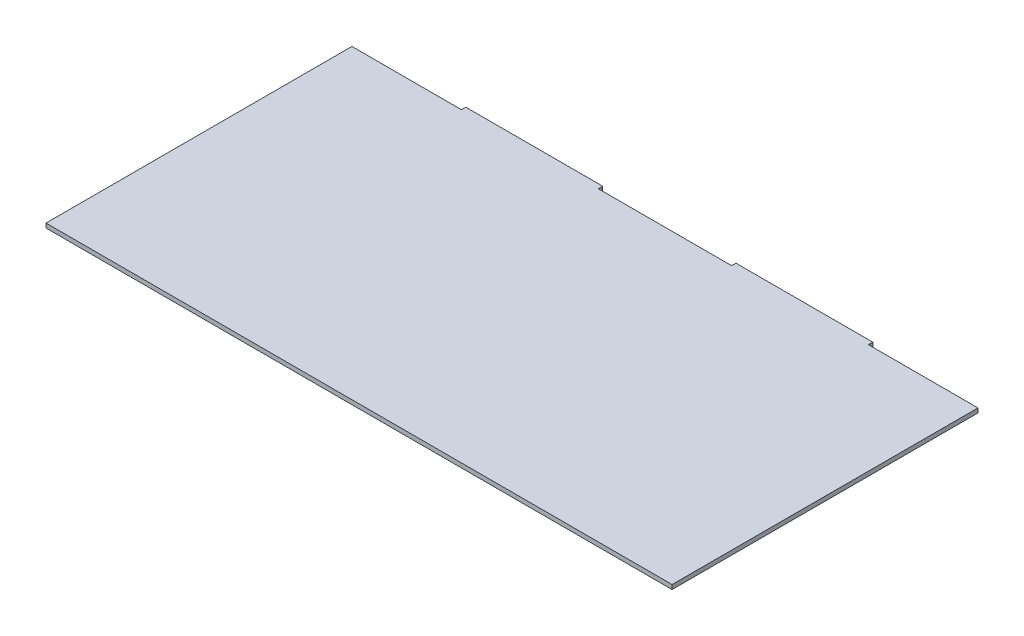
SolidWorks part; units mm, degrees
material "6061-T6 (SS)"
ref_plane "X-Y Datum" through (0, 0, 0) normal (0, 0, 1) x (1, 0, 0)
ref_plane "X-Z Datum" through (0, 0, 0) normal (0, 1, 0) x (1, 0, 0)
ref_plane "Y-Z Datum" through (0, 0, 0) normal (1, 0, 0) x (0, 0, -1)
sketch "Sketch1" plane through (0, 0, 0) normal (0, 0, 1) x (1, 0, 0)
  line L1 (-228.6, -1.5875) -> (228.6, -1.5875)
  line L2 (-228.6, -1.5875) -> (-228.6, 1.5875)
  line L3 (-228.6, 1.5875) -> (228.6, 1.5875)
  line L4 (228.6, -1.5875) -> (228.6, 1.5875)
  line L5 (-228.6, -1.5875) -> (228.6, 1.5875) construction
  line L6 (-228.6, 1.5875) -> (228.6, -1.5875) construction
  point P0 (0, 0)
  dimension "D1" = 3.175
  dimension "D2" = 457.2
extrude "Boss-Extrude1" add sketch "Sketch1" along normal blind 223.38
sketch "Sketch2" plane through (0, 0, 0) normal (0, 0, -1) x (-1, 0, 0)
  line L1 (-148.6115, 1.5875) -> (-48.6115, 1.5875)
  line L2 (-148.6115, 1.5875) -> (-148.6115, -1.5875)
  line L3 (-148.6115, -1.5875) -> (-48.6115, -1.5875)
  line L4 (-48.6115, 1.5875) -> (-48.6115, -1.5875)
  line L5 (48.6115, 1.5875) -> (148.6115, 1.5875)
  line L6 (48.6115, 1.5875) -> (48.6115, -1.5875)
  line L7 (48.6115, -1.5875) -> (148.6115, -1.5875)
  line L8 (148.6115, 1.5875) -> (148.6115, -1.5875)
extrude "Boss-Extrude2" add sketch "Sketch2" along normal blind 3.175
